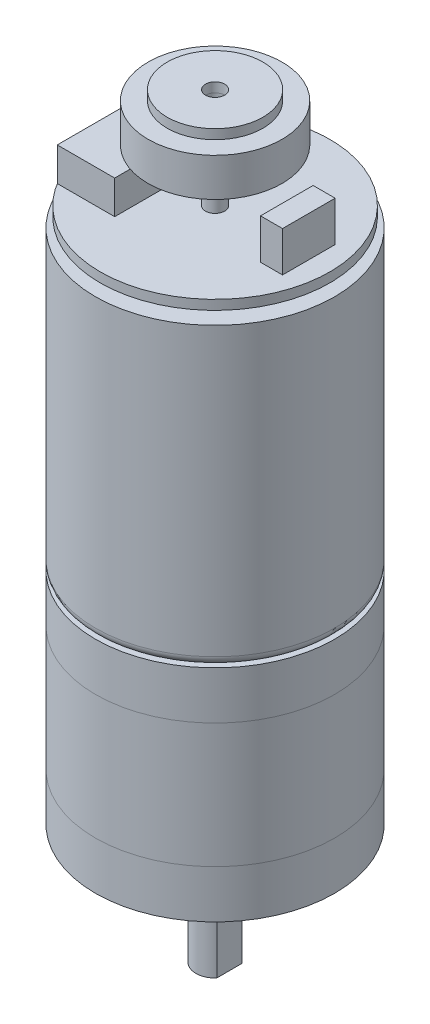
SolidWorks part; units mm, degrees
material "EN 10025-2-S355JR"
ref_plane "Front Plane" through (0, 0, 0) normal (0, 0, 1) x (1, 0, 0)
ref_plane "Top Plane" through (0, 0, 0) normal (0, 1, 0) x (1, 0, 0)
ref_plane "Right Plane" through (0, 0, 0) normal (1, 0, 0) x (0, 0, -1)
sketch "Sketch1" plane through (0, 0, 0) normal (0, 1, 0) x (1, 0, 0)
  line L0 (0, -12.5) -> (0, 12.5) construction
  line L1 (-12.5, 0) -> (12.5, 0) construction
  circle A0 centre (0, 0) radius 12.5
  circle A1 centre (-8.5, 0) radius 1.5
  circle A2 centre (8.5, 0) radius 1.5
  dimension "D1" = 25
  dimension "D2" = 3
  dimension "D3" = 17
extrude "Boss-Extrude1" add sketch "Sketch1" along normal blind 5
sketch "Sketch2" plane through (0, 5, 0) normal (0, 1, 0) x (1, 0, 0)
  circle A0 centre (0, 0) radius 12.5
extrude "Boss-Extrude2" add sketch "Sketch2" along normal blind 13 separate body
sketch "Sketch3" plane through (0, 18, 0) normal (0, 1, 0) x (1, 0, 0)
  circle A0 centre (0, 0) radius 12.5
extrude "Boss-Extrude3" add sketch "Sketch3" along normal blind 5 separate body
sketch "Sketch4" plane through (0, 23, 0) normal (0, 1, 0) x (1, 0, 0)
  circle A0 centre (0, 0) radius 12.5
extrude "Boss-Extrude4" add sketch "Sketch4" along normal blind 31 separate body
fillet "Fillet2" radius 1 1 edges at (0, 23, 12.5)
sketch "Sketch5" plane through (0, 54, 0) normal (0, 1, 0) x (1, 0, 0)
  circle A0 centre (0, 0) radius 2.5
  dimension "D1" = 5
extrude "Boss-Extrude5" add sketch "Sketch5" along normal blind 1 separate body
sketch "Sketch6" plane through (0, 55, 0) normal (0, 1, 0) x (1, 0, 0)
  circle A0 centre (0, 0) radius 12
  dimension "D1" = 24
extrude "Boss-Extrude6" add sketch "Sketch6" along normal blind 1 separate body
sketch "Sketch7" plane through (0, 56, 0) normal (0, 1, 0) x (1, 0, 0)
  circle A0 centre (0, 0) radius 1
  dimension "D1" = 2
extrude "Boss-Extrude7" add sketch "Sketch7" along normal blind 5 separate body
sketch "Sketch8" plane through (0, 61, 0) normal (0, 1, 0) x (1, 0, 0)
  circle A0 centre (0, 0) radius 4
  dimension "D1" = 8
extrude "Boss-Extrude8" add sketch "Sketch8" along normal blind 0.5 separate body
sketch "Sketch9" plane through (0, 61.5, 0) normal (0, 1, 0) x (1, 0, 0)
  circle A0 centre (0, 0) radius 7
  dimension "D1" = 14
extrude "Boss-Extrude9" add sketch "Sketch9" along normal blind 4 separate body
sketch "Sketch10" plane through (0, 65.5, 0) normal (0, 1, 0) x (1, 0, 0)
  circle A0 centre (0, 0) radius 5
  dimension "D1" = 10
extrude "Boss-Extrude10" add sketch "Sketch10" along normal blind 1 separate body
sketch "Sketch11" plane through (0, 66.5, 0) normal (0, 1, 0) x (1, 0, 0)
  circle A0 centre (0, 0) radius 1
  dimension "D1" = 2
extrude "Cut-Extrude1" cut sketch "Sketch11" against normal blind 2
sketch "Sketch12" plane through (0, 0, 0) normal (0, -1, 0) x (1, 0, 0)
  circle A0 centre (0, 0) radius 3.5
  dimension "D1" = 7
extrude "Boss-Extrude11" add sketch "Sketch12" along normal blind 2.5 separate body
sketch "Sketch13" plane through (0, -2.5, 0) normal (0, -1, 0) x (1, 0, 0)
  circle A0 centre (0, 0) radius 2
  dimension "D1" = 4
extrude "Boss-Extrude12" add sketch "Sketch13" along normal blind 10 separate body
sketch "Sketch14" plane through (0, -12.5, 0) normal (0, -1, 0) x (1, 0, 0)
  line L0 (0, 2) -> (0, -2) construction
  line L1 (1.5, 1.3229) -> (1.5, -1.3229)
  arc A1 (1.5, -1.3229) -> (1.5, 1.3229) centre (0, 0) ccw
  dimension "D1" = 1.5
extrude "Cut-Extrude2" cut sketch "Sketch14" against normal blind 7.8
sketch "Sketch15" plane through (0, 56, 0) normal (0, 1, 0) x (1, 0, 0)
  line L0 (-12, 0) -> (12, 0) construction
  line L1 (0, -12) -> (0, 12) construction
  line L3 (-10.2439, -6.25) -> (-4.2439, -6.25)
  line L4 (-10.2439, -6.25) -> (-10.2439, 6.25)
  line L5 (-10.2439, 6.25) -> (-4.2439, 6.25)
  line L6 (-4.2439, -6.25) -> (-4.2439, 6.25)
  line L7 (-10.2439, -6.25) -> (-4.2439, 6.25) construction
  line L8 (-10.2439, 6.25) -> (-4.2439, -6.25) construction
  circle A0 centre (0, 0) radius 12 construction
  point P8 (-7.2439, 0)
  dimension "D1" = 6
  dimension "D2" = 12.5
extrude "Boss-Extrude13" add sketch "Sketch15" along normal blind 3.5 separate body
sketch "Sketch16" plane through (0, 56, 0) normal (0, 1, 0) x (1, 0, 0)
  line L0 (0, -12) -> (0, 12) construction
  line L1 (-12, 0) -> (12, 0) construction
  line L3 (7.5, -2.75) -> (9.8, -2.75)
  line L4 (7.5, -2.75) -> (7.5, 2.75)
  line L5 (7.5, 2.75) -> (9.8, 2.75)
  line L6 (9.8, -2.75) -> (9.8, 2.75)
  line L7 (7.5, -2.75) -> (9.8, 2.75) construction
  line L8 (7.5, 2.75) -> (9.8, -2.75) construction
  circle A0 centre (0, 0) radius 12 construction
  point P7 (8.65, 0)
  dimension "D1" = 5.5
  dimension "D2" = 2.3
  dimension "D3" = 7.5
extrude "Boss-Extrude14" add sketch "Sketch16" along normal blind 4.2 separate body
sketch "Sketch17" [suppressed] plane through (0, 54.2, 0) normal (0, 1, 0) x (1, 0, 0)
  line L0 (9.8, 2.75) -> (7.5, 2.75) construction
  line L2 (9.8, -2.75) -> (9.8, 2.75) construction
  line L4 (7.5, 2.75) -> (7.5, -2.75) construction
  line L5 (7.5, -2.75) -> (9.8, -2.75) construction
  line L6 (9.8, 2.75) -> (7.5, 2.75) construction
  line L7 (9.8, -2.75) -> (9.8, 2.75) construction
  line L8 (7.5, 2.75) -> (7.5, -2.75) construction
  line L9 (7.5, -2.75) -> (9.8, -2.75) construction
  line L10 (7.5, -2.75) -> (9, -2.75)
  line L11 (9, -2.75) -> (9, 2.75)
  line L12 (9, 2.75) -> (7.5, 2.75)
  line L13 (7.5, 2.75) -> (7.5, -2.75)
  dimension "D1" = 1.5
extrude "Boss-Extrude15" [suppressed] add sketch "Sketch17" along normal blind 3.5
other "Freeze***"
